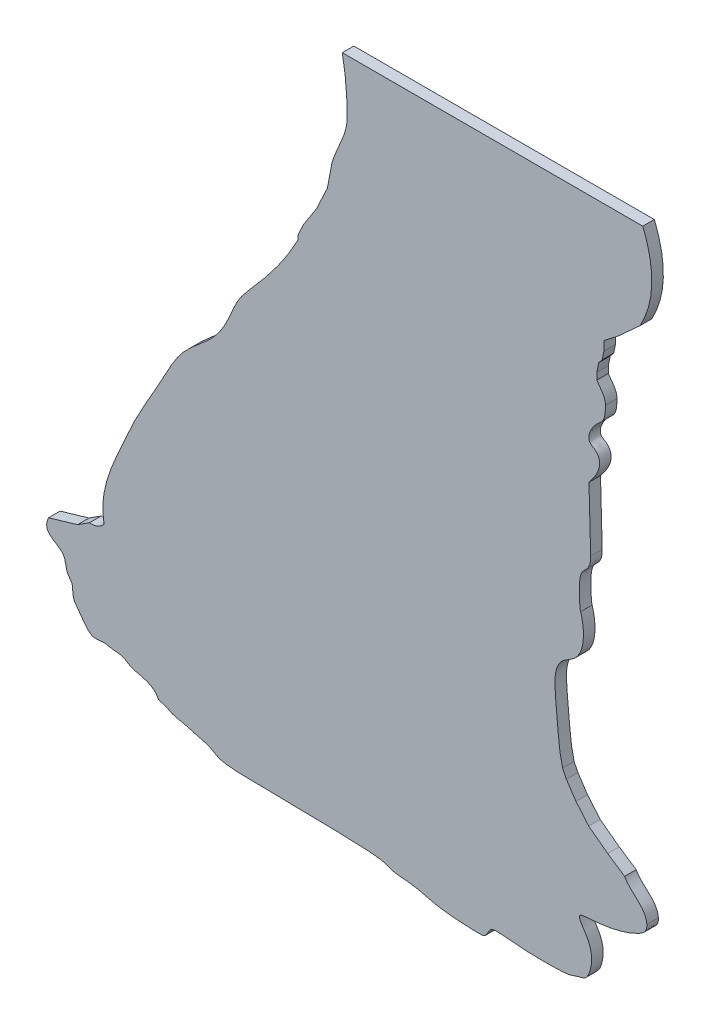
SolidWorks part; units mm, degrees
ref_plane "Front Plane" through (0, 0, 0) normal (0, 0, 1) x (1, 0, 0)
ref_plane "Top Plane" through (0, 0, 0) normal (0, 1, 0) x (1, 0, 0)
ref_plane "Right Plane" through (0, 0, 0) normal (1, 0, 0) x (0, 0, -1)
sketch "Sketch1" plane through (0, 0, 0) normal (0, 0, 1) x (1, 0, 0)
  line L0 (134.6667, 500.5) -> (673.3333, 500.5) construction
  line L2 (167.2022, 42.2012) -> (162.5517, 45.3095)
  line L3 (162.5517, 45.3095) -> (157.3147, 49.2233)
  line L4 (157.3147, 49.2233) -> (153.7929, 53.3936)
  line L5 (153.7929, 53.3936) -> (151.1787, 57.3127)
  line L6 (151.1787, 57.3127) -> (150.1126, 59.4633)
  line L7 (157.3755, 131.2295) -> (157.854, 113.8805)
  line L8 (159.5344, 156.6595) -> (159.5344, 158.498)
  line L9 (159.5344, 158.498) -> (160.0825, 161.1123)
  line L10 (160.0825, 161.1123) -> (161.0243, 162.2425)
  line L11 (161.0243, 162.2425) -> (161.5128, 164.5724)
  line L12 (161.5128, 164.5724) -> (161.5128, 167.1023)
  line L13 (161.5128, 167.1023) -> (165.1835, 169.9013)
  line L14 (165.1835, 169.9013) -> (171.472, 175.6217)
  line L15 (86.5908, 171.7678) -> (85.3882, 165.3811)
  line L16 (89.473, 199.6877) -> (172.1964, 199.6877)
  line L17 (85.3882, 165.3811) -> (82.4023, 158.9826)
  line L18 (82.4023, 158.9826) -> (78.8266, 153.4325)
  line L19 (78.8266, 153.4325) -> (77.3096, 150.1819)
  line L20 (77.3096, 150.1819) -> (77.3096, 148.973)
  spline S0 degree 1 poles (8.6124, 48.3831) (16.6111, 50.7357) knots 0 0 1 1
  spline S1 degree 1 poles (19.9047, 52.853) (16.6111, 50.7357) knots 0 0 1 1
  spline S2 degree 3 poles (23.9041, 54.4997) (22.542, 62.0444) (27.1512, 71.7199) (33.1716, 85.6736) (39.4703, 95.7444) (45.0444, 107.3971) (54.1548, 113.0729) (58.3579, 120.6747) (60.6418, 126.7915) (68.4166, 135.2748) (73.9208, 142.4894) (77.3096, 148.973) knots 0 0 0 0 0.194457 0.285904 0.412664 0.517827 0.629269 0.691339 0.750377 0.804905 1 1 1 1
  spline S3 degree 2 poles (19.9047, 52.853) (22.4371, 52.6083) (23.9041, 54.4997) knots 0 0 0 1 1 1
  spline S4 degree 3 poles (8.6124, 48.3831) (6.5691, 43.9628) (13.6478, 43.7296) (13.2535, 37.9915) (15.2259, 36.1128) (15.2445, 34.2074) (15.4257, 32.4092) (16.9812, 30.3171) (18.455, 28.2086) (20.7273, 25.6089) (23.6404, 26.5196) (26.3788, 25.705) (29.0077, 25.795) (31.226, 24.0079) (34.9468, 23.3493) (38.0007, 22.2222) (38.8831, 20.145) knots 0 0 0 0 0.18572 0.273851 0.320038 0.350192 0.393849 0.435551 0.514834 0.569195 0.638874 0.687587 0.755837 0.801068 0.865551 1 1 1 1
  spline S5 degree 3 poles (38.8831, 20.145) (41.2875, 19.5656) (42.3458, 18.5073) (45.4199, 18.1546) (49.7538, 16.7939) (52.7775, 16.1892) (54.7934, 14.8285) (56.3556, 14.1734) (60.1352, 13.7702) (61.5463, 13.7702) (99.2418, 13.2159) (101.2856, 12.2232) (103.9594, 11.2977) (106.3246, 11.2977) (111.5693, 10.5778) (115.1686, 9.2409) (123.9098, 8.5211) (128.0233, 8.5211) (128.9488, 8.7267) (129.9772, 10.7835) (131.0055, 11.8119) (139.3353, 10.7835) (144.7857, 10.7835) (151.9843, 10.7835) (154.3496, 12.1204) (156.7148, 12.1204) (158.1545, 16.0282) (158.1545, 19.319) (157.3318, 21.6842) (156.4063, 23.3296) (153.7325, 27.1346) (157.3189, 27.1346) (163.0629, 27.7755) (167.4392, 28.9243) (170.3933, 30.1004) (172.855, 31.5228) (173.32, 32.5895) (173.32, 33.793) knots 0 0 0 0 0.028571 0.057143 0.085714 0.114286 0.142857 0.171429 0.2 0.228571 0.257143 0.285714 0.314286 0.342857 0.371429 0.4 0.428571 0.457143 0.485714 0.514286 0.542857 0.571429 0.6 0.628571 0.657143 0.685714 0.714286 0.742857 0.771429 0.8 0.828571 0.857143 0.885714 0.914286 0.942857 0.971429 1 1 1 1
  spline S6 degree 3 poles (173.32, 33.793) (173.0564, 37.6266) (168.8406, 39.1122) (167.2022, 42.2012) knots 0 0 0 0 1 1 1 1
  spline S7 degree 3 poles (150.1126, 59.4633) (148.9568, 63.837) (148.9486, 71.4394) (146.8505, 84.0514) (156.4694, 88.1502) (156.2475, 95.5102) (155.0853, 99.2556) knots 0 0 0 0 0.308783 0.618237 0.704406 1 1 1 1
  spline S8 degree 3 poles (157.854, 113.8805) (157.8564, 113.8699) (157.8506, 110.688) (155.3081, 109.3846) (154.4188, 105.0533) (154.8696, 99.4834) (155.0853, 99.2556) knots 0 0 0 0 0.124799 0.365608 0.555267 1 1 1 1
  spline S9 degree 3 poles (161.8927, 151.8072) (161.9125, 149.0313) (161.4499, 147.7916) (158.4451, 145.386) (156.1309, 141.3803) (158.8302, 140.0435) (161.6487, 137.4079) (159.4597, 133.7277) (157.3755, 131.2295) knots 0 0 0 0 0.190659 0.228613 0.488803 0.534056 0.585176 1 1 1 1
  spline S10 degree 3 poles (159.5344, 156.6595) (160.7867, 154.8399) (162.0055, 153.6124) (161.8927, 151.8072) knots 0 0 0 0 1 1 1 1
  spline S11 degree 2 poles (172.1964, 199.6877) (177.5125, 186.6119) (171.472, 175.6217) knots 0 0 0 1 1 1
  spline S12 degree 3 poles (89.473, 199.6877) (90.4497, 194.8375) (90.826, 189.8378) (90.8383, 180.2807) (87.6783, 176.1914) (86.5908, 171.7678) knots 0 0 0 0 0.517811 0.520823 1 1 1 1
  point P81 (0, 0)
  point P95 (0, 0)
extrude "Boss-Extrude2" add sketch "Sketch1" along normal blind 3.175
